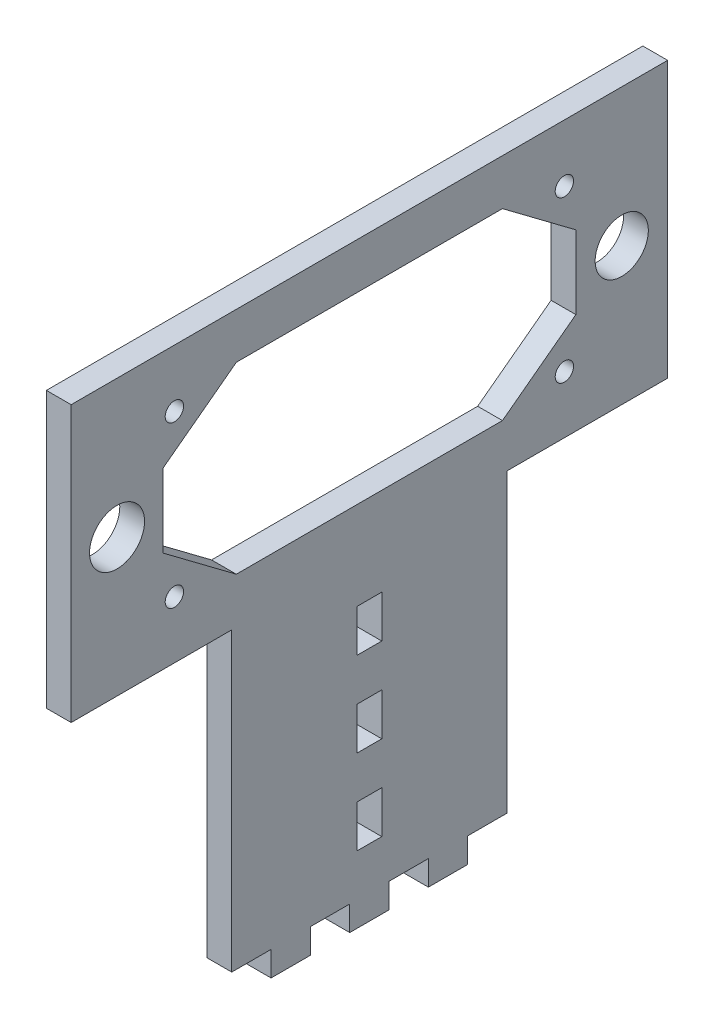
SolidWorks part; units mm, degrees
ref_plane "Ön Düzlem" through (0, 0, 0) normal (0, 0, 1) x (1, 0, 0)
ref_plane "Üst Düzlem" through (0, 0, 0) normal (0, 1, 0) x (1, 0, 0)
ref_plane "Sağ Düzlem" through (0, 0, 0) normal (1, 0, 0) x (0, 0, -1)
sketch "Sketch1" plane through (0, 0, 0) normal (1, 0, 0) x (0, 0, -1)
  line L0 (10.7143, -32.5) -> (6.4286, -32.5)
  line L4 (-15, -29.8) -> (-15, 2.5)
  line L8 (2.1429, -32.5) -> (-2.1429, -32.5)
  line L10 (-6.4286, -32.5) -> (-10.7143, -32.5)
  line L12 (-10.7143, -32.5) -> (-10.7143, -29.8)
  line L13 (-6.4286, -32.5) -> (-6.4286, -29.8)
  line L14 (-15, -29.8) -> (-10.7143, -29.8)
  line L15 (-2.1429, -32.5) -> (-2.1429, -29.8)
  line L16 (2.1429, -32.5) -> (2.1429, -29.8)
  line L17 (6.4286, -32.5) -> (6.4286, -29.8)
  line L18 (10.7143, -32.5) -> (10.7143, -29.8)
  line L19 (-6.4286, -29.8) -> (-2.1429, -29.8)
  line L20 (2.1429, -29.8) -> (6.4286, -29.8)
  line L21 (10.7143, -29.8) -> (15, -29.8)
  line L27 (15, -29.8) -> (15, 2.5)
  line L28 (1.35, -2.1143) -> (1.35, -6.7286)
  line L30 (1.35, -11.3429) -> (1.35, -15.9571)
  line L31 (32.5, 32.5) -> (-32.5, 32.5)
  line L32 (1.35, -20.5714) -> (1.35, -25.1857)
  line L35 (-1.35, -2.1143) -> (1.35, -2.1143)
  line L36 (-1.35, -20.5714) -> (-1.35, -25.1857)
  line L38 (-1.35, -11.3429) -> (-1.35, -15.9571)
  line L39 (32.5, 32.5) -> (32.5, 2.5)
  line L40 (-1.35, -2.1143) -> (-1.35, -6.7286)
  line L41 (32.5, 2.5) -> (15, 2.5)
  line L42 (-1.35, -6.7286) -> (1.35, -6.7286)
  line L43 (1.35, -11.3429) -> (-1.35, -11.3429)
  line L44 (-1.35, -15.9571) -> (1.35, -15.9571)
  line L45 (1.35, -20.5714) -> (-1.35, -20.5714)
  line L46 (-1.35, -25.1857) -> (1.35, -25.1857)
  line L47 (-32.5, 2.5) -> (-32.5, 32.5)
  line L49 (0, 7.5) -> (14.5, 7.5)
  line L50 (0, 7.5) -> (-14.5, 7.5)
  line L51 (-22.5, 13.5) -> (-22.5, 21.5)
  line L52 (-14.5, 27.5) -> (14.5, 27.5)
  line L53 (22.5, 21.5) -> (22.5, 13.5)
  line L54 (-22.5, 21.5) -> (-14.5, 27.5)
  line L55 (-14.5, 7.5) -> (-22.5, 13.5)
  line L56 (14.5, 27.5) -> (22.5, 21.5)
  line L57 (14.5, 7.5) -> (22.5, 13.5)
  line L58 (-15, 2.5) -> (-32.5, 2.5)
  circle A1 centre (21.25, 26.25) radius 1
  circle A2 centre (21.25, 8.75) radius 1
  circle A3 centre (-21.25, 8.75) radius 1
  circle A4 centre (-21.25, 26.25) radius 1
  circle A5 centre (-27.5, 17.5) radius 3
  circle A6 centre (27.5, 17.5) radius 2.9
  point P0 (0, 0)
extrude "Boss-Extrude1" add sketch "Sketch1" against normal blind 2.7
